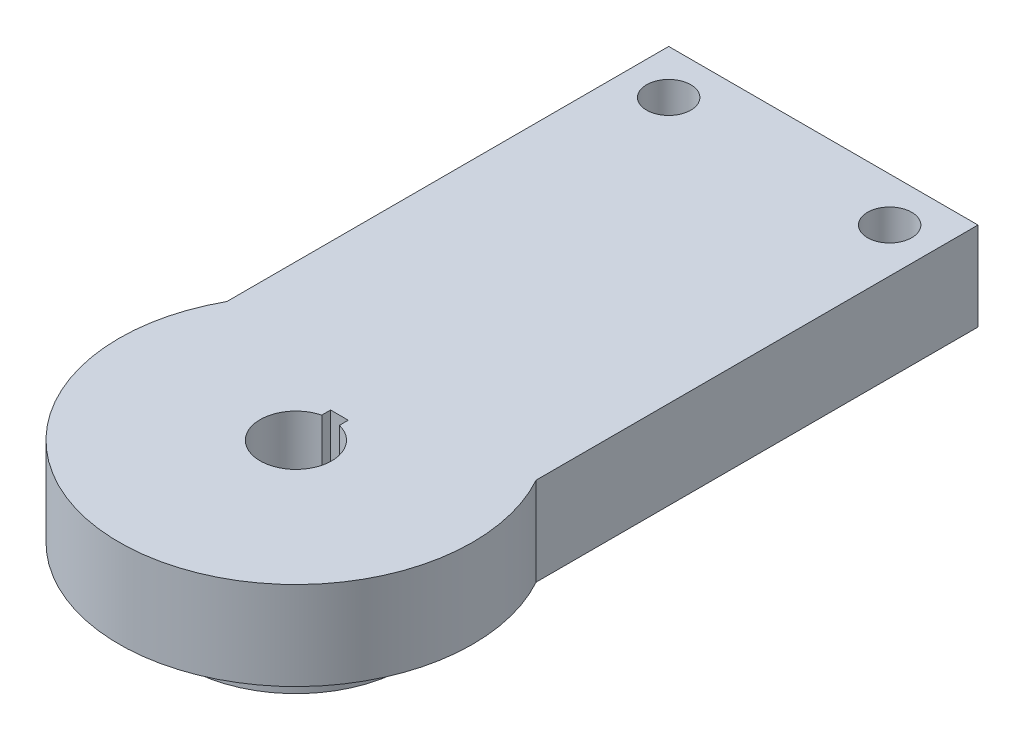
SolidWorks part; units mm, degrees
ref_plane "Front Plane" through (0, 0, 0) normal (0, 0, 1) x (1, 0, 0)
ref_plane "Top Plane" through (0, 0, 0) normal (0, 1, 0) x (1, 0, 0)
ref_plane "Right Plane" through (0, 0, 0) normal (1, 0, 0) x (0, 0, -1)
sketch "Sketch1" plane through (0, 0, 0) normal (0, 1, 0) x (1, 0, 0)
  circle A21 centre (0, 0) radius 20
  dimension "D1" = 40
extrude "Boss-Extrude1" add sketch "Sketch1" along normal blind 10
sketch "Sketch2" plane through (0, 10, 0) normal (0, 1, 0) x (1, 0, 0)
  line L0 (-1, 4.9246) -> (-1, 3.9246)
  line L1 (-1, 4.9246) -> (1, 4.9246)
  line L2 (1, 4.9246) -> (1, 3.9246)
  arc A0 (-1, 3.9246) -> (1, 3.9246) centre (0, 0) ccw
  point P5 (0, 4.9246)
  dimension "D1" = 8.1
  dimension "D2" = 1
  dimension "D3" = 2
extrude "Cut-Extrude1" cut sketch "Sketch2" against normal through all
sketch "Sketch3" plane through (0, 0, 0) normal (0, 1, 0) x (1, 0, 0)
  line L0 (-17.5, 59.6825) -> (-17.5, 9.6825)
  line L1 (-17.5, 59.6825) -> (17.5, 59.6825)
  line L2 (17.5, 59.6825) -> (17.5, 9.6825)
  circle A0 centre (0, 0) radius 20 construction
  arc A1 (17.5, 9.6825) -> (-17.5, 9.6825) centre (0, 0) ccw
  point P6 (0, 59.6825)
  dimension "D1" = 35
  dimension "D2" = 50
extrude "Boss-Extrude2" add sketch "Sketch3" along normal up to surface (10 mm away) up to face at (0, 10, -2.431)
sketch "Sketch4" plane through (0, 0, 0) normal (0, -1, 0) x (1, 0, 0)
  line L0 (-12.5, -54.6825) -> (12.5, -54.6825) construction
  line L1 (17.5, -59.6825) -> (-17.5, -59.6825) construction
  circle A0 centre (-12.5, -54.6825) radius 2.5
  circle A1 centre (12.5, -54.6825) radius 2.5
  point P6 (0, -54.6825)
  dimension "D1" = 5
  dimension "D2" = 5
  dimension "D3" = 25
extrude "Cut-Extrude2" cut sketch "Sketch4" against normal through all
sketch "Sketch5" plane through (0, 0, 0) normal (0, -1, 0) x (1, 0, 0)
  line L0 (-1, -3.9246) -> (-1, -4.9246)
  line L1 (-1, -4.9246) -> (1, -4.9246)
  line L2 (1, -4.9246) -> (1, -3.9246)
  circle A0 centre (0, 0) radius 12.5
  arc A1 (1, -3.9246) -> (-1, -3.9246) centre (0, 0) ccw
  dimension "D1" = 25
extrude "Boss-Extrude3" add sketch "Sketch5" along normal blind 6
